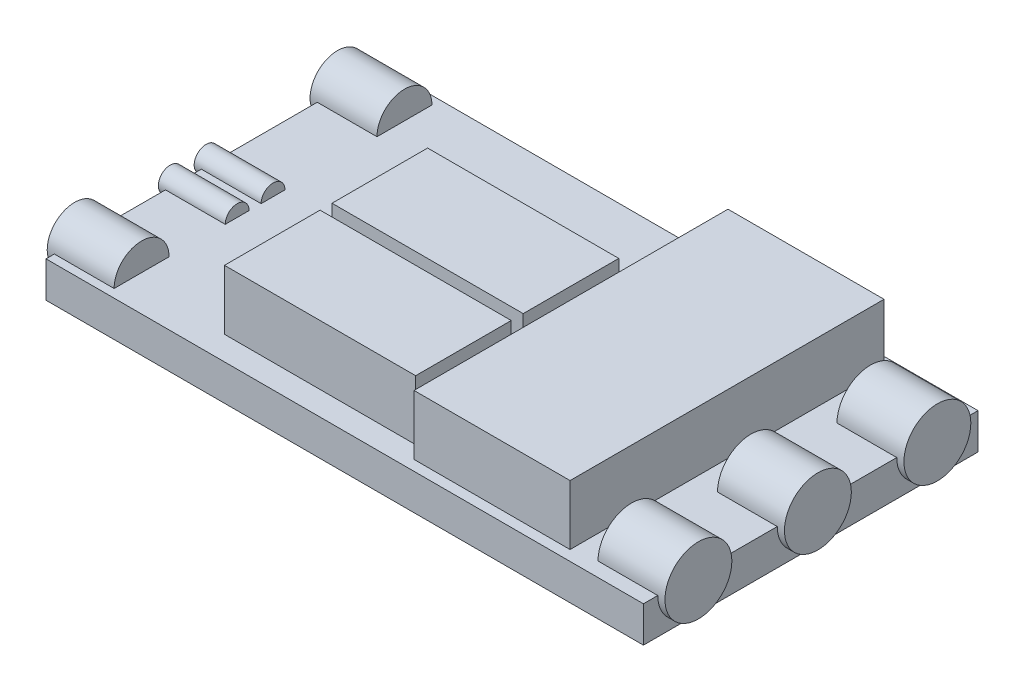
SolidWorks part; units mm, degrees
ref_plane "Ebene vorne" through (0, 0, 0) normal (0, 0, 1) x (1, 0, 0)
ref_plane "Ebene oben" through (0, 0, 0) normal (0, 1, 0) x (1, 0, 0)
ref_plane "Ebene rechts" through (0, 0, 0) normal (1, 0, 0) x (0, 0, -1)
sketch "Skizze1" plane through (0, 0, 0) normal (0, 1, 0) x (1, 0, 0)
  line L1 (-12.5, -7) -> (12.5, -7)
  line L2 (-12.5, -7) -> (-12.5, 7)
  line L3 (-12.5, 7) -> (12.5, 7)
  line L4 (12.5, -7) -> (12.5, 7)
  line L5 (-12.5, -7) -> (12.5, 7) construction
  line L6 (-12.5, 7) -> (12.5, -7) construction
  point P0 (0, 0)
  dimension "D1" = 25
  dimension "D2" = 14
extrude "Platine" add sketch "Skizze1" along normal blind 1.5
sketch "Skizze2" plane through (0, 1.5, 0) normal (0, 1, 0) x (1, 0, 0)
  line L1 (2.4683, -6.5693) -> (8.999, -6.5693)
  line L2 (2.4683, -6.5693) -> (2.4683, 6.5693)
  line L3 (2.4683, 6.5693) -> (8.999, 6.5693)
  line L4 (8.999, -6.5693) -> (8.999, 6.5693)
  line L5 (2.4683, -6.5693) -> (8.999, 6.5693) construction
  line L6 (2.4683, 6.5693) -> (8.999, -6.5693) construction
  point P0 (5.7337, 0)
extrude "MOSFETs" add sketch "Skizze2" along normal blind 2.5
sketch "Skizze4" plane through (0, 1.5, 0) normal (0, 1, 0) x (1, 0, 0)
  line L0 (-12.5, -7) -> (12.5, -7) construction
  line L1 (1.9683, -6) -> (-6.0317, -6)
  line L2 (1.9683, -6) -> (1.9683, -2)
  line L3 (1.9683, -2) -> (-6.0317, -2)
  line L4 (-6.0317, -6) -> (-6.0317, -2)
  line L5 (1.9683, -1.5) -> (-6.0317, -1.5)
  line L6 (1.9683, -1.5) -> (1.9683, 2.5)
  line L7 (1.9683, 2.5) -> (-6.0317, 2.5)
  line L8 (-6.0317, -1.5) -> (-6.0317, 2.5)
  line L9 (2.4683, 6.5693) -> (2.4683, -6.5693) construction
  dimension "D1" = 0.5
  dimension "D2" = 1
  dimension "D3" = 4
  dimension "D4" = 8
  dimension "D5" = 0.5
extrude "Weitere_ICs" add sketch "Skizze4" along normal blind 2.5
sketch "Skizze5" plane through (12.5, 0, 0) normal (1, 0, 0) x (0, 0, -1)
  line L0 (-7, 1.5) -> (7, 1.5) construction
  line L1 (0, -1.3214) -> (0, 7.1636) construction
  line L2 (-7, 1.5) -> (-7, 0) construction
  circle A0 centre (-5, 1.5) radius 1.4
  circle A1 centre (0, 1.5) radius 1.4
  circle A2 centre (5, 1.5) radius 1.4
  dimension "D1" = 2.8
  dimension "D2" = 2
extrude "Lot_Motor" add sketch "Skizze5" against normal blind 2.5 and the other way blind 0.3
sketch "Skizze6" plane through (-12.5, 0, 0) normal (-1, 0, 0) x (0, 0, 1)
  line L0 (-7, 1.5) -> (7, 1.5) construction
  line L1 (0, 6.8019) -> (0, -3.8098) construction
  line L2 (-7, 1.5) -> (-7, 0) construction
  circle A0 centre (-5.5, 1.5) radius 1.15
  circle A1 centre (5.5, 1.5) radius 1.15
  dimension "D1" = 2.3
  dimension "D2" = 1.5
extrude "Lot_PDB" add sketch "Skizze6" against normal blind 2.5 and the other way blind 0.3
sketch "Skizze7" plane through (-12.5, 0, 0) normal (-1, 0, 0) x (0, 0, 1)
  line L0 (-4.35, 1.5) -> (4.35, 1.5) construction
  circle A0 centre (1.5, 1.5) radius 0.5
  circle A1 centre (0, 1.5) radius 0.5
  dimension "D1" = 1
  dimension "D2" = 1.5
extrude "Lot_FC" add sketch "Skizze7" against normal blind 2.5 and the other way blind 0.3
sketch "Skizze8" plane through (12.8, 0, 0) normal (1, 0, 0) x (0, 0, -1)
  point P0 (5, 1.5)
  point P1 (0, 1.5)
  point P2 (-5, 1.5)
sketch "Skizze10" plane through (-12.8, 0, 0) normal (-1, 0, 0) x (0, 0, 1)
  point P0 (5.5, 1.5)
  point P1 (1.5, 1.5)
  point P3 (0, 1.5)
  point P5 (-5.5, 1.5)
sketch "0_0_Point" plane through (12.8, 0, 0) normal (1, 0, 0) x (0, 0, -1)
  point P0 (5, 1.5)
other "0_0" parameters "Durchmesser"=2, "Stumpflänge"=2
ref_axis "Achse1" through (22.8, 1.5, -5) along (-1, 0, 0)
sketch "0_1_Point" plane through (12.8, 0, 0) normal (1, 0, 0) x (0, 0, -1)
  point P0 (0, 1.5)
other "0_1" parameters "Durchmesser"=2, "Stumpflänge"=2
ref_axis "Achse2" through (22.8, 1.5, 0) along (-1, 0, 0)
sketch "0_2_Point" plane through (12.8, 0, 0) normal (1, 0, 0) x (0, 0, -1)
  point P0 (-5, 1.5)
other "0_2" parameters "Durchmesser"=2, "Stumpflänge"=2
ref_axis "Achse3" through (22.8, 1.5, 5) along (-1, 0, 0)
sketch "1_0_Point" plane through (-12.8, 0, 0) normal (-1, 0, 0) x (0, 0, 1)
  point P0 (-5.5, 1.5)
other "1_0" parameters "Durchmesser"=2, "Stumpflänge"=2
ref_axis "Achse4" through (-22.8, 1.5, -5.5) along (1, 0, 0)
sketch "1_1_Point" plane through (-12.8, 0, 0) normal (-1, 0, 0) x (0, 0, 1)
  point P0 (5.5, 1.5)
other "1_1" parameters "Durchmesser"=2, "Stumpflänge"=2
ref_axis "Achse5" through (-22.8, 1.5, 5.5) along (1, 0, 0)
sketch "2_0_Point" plane through (-12.8, 0, 0) normal (-1, 0, 0) x (0, 0, 1)
  point P0 (0, 1.5)
other "2_0" parameters "Durchmesser"=2, "Stumpflänge"=2
ref_axis "Achse6" through (-22.8, 1.5, 0) along (1, 0, 0)
sketch "2_1_Point" plane through (-12.8, 0, 0) normal (-1, 0, 0) x (0, 0, 1)
  point P0 (1.5, 1.5)
other "2_1" parameters "Durchmesser"=2, "Stumpflänge"=2
ref_axis "Achse7" through (-22.8, 1.5, 1.5) along (1, 0, 0)
